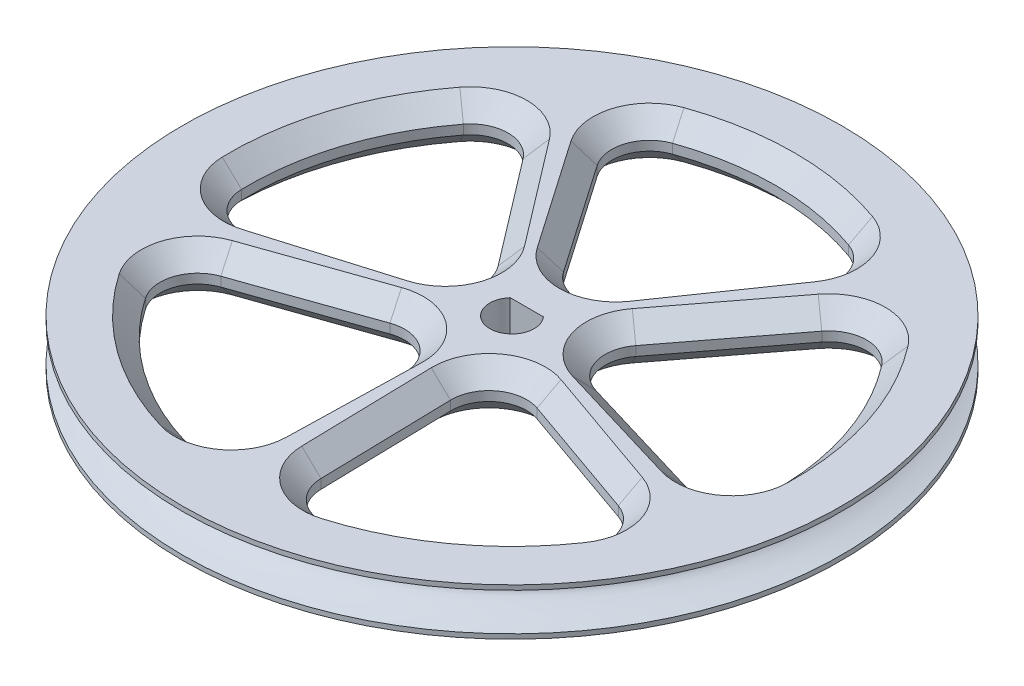
SolidWorks part; units mm, degrees
ref_plane "Front Plane" through (0, 0, 0) normal (0, 0, 1) x (1, 0, 0)
ref_plane "Top Plane" through (0, 0, 0) normal (0, 1, 0) x (1, 0, 0)
ref_plane "Right Plane" through (0, 0, 0) normal (1, 0, 0) x (0, 0, -1)
sketch "Sketch1" plane through (0, 0, 0) normal (0, 1, 0) x (1, 0, 0)
  circle A0 centre (0, 0) radius 22.225
  dimension "D1" = 44.45
extrude "Boss-Extrude1" add sketch "Sketch1" along normal blind 3.175
sketch "Sketch2" plane through (0, 3.175, 0) normal (0, 1, 0) x (1, 0, 0)
  line L0 (-1.118, 1) -> (1.118, 1)
  line L1 (0, 1) -> (0, -1.5) construction
  arc A0 (-1.118, 1) -> (1.118, 1) centre (0, 0) ccw
  dimension "D1" = 3
  dimension "D2" = 2.5
sketch "Sketch3" plane through (0, 3.175, 0) normal (0, 1, 0) x (1, 0, 0)
  line L0 (0, 0) -> (11.1125, 19.2474) construction
  line L1 (0, 0) -> (-11.1125, 19.2474) construction
  line L2 (-7.1774, 12.921) -> (-2.0893, 5.5618)
  line L3 (2.0893, 5.5618) -> (7.1774, 12.921)
  line L4 (0, 2.54) -> (0, 0) construction
  line L5 (0, 0) -> (0, 22.225) construction
  line L6 (10.0706, 10.819) -> (4.6439, 3.7057)
  line L7 (5.9352, -0.2683) -> (14.5066, -2.8333)
  line L8 (13.4014, -6.2345) -> (4.9594, -3.2715)
  line L9 (1.5789, -5.7276) -> (1.7881, -14.6721)
  line L10 (-1.7881, -14.6721) -> (-1.5789, -5.7276)
  line L11 (-4.9594, -3.2715) -> (-13.4014, -6.2345)
  line L12 (-14.5066, -2.8333) -> (-5.9352, -0.2683)
  line L13 (-4.6439, 3.7057) -> (-10.0706, 10.819)
  circle A0 centre (0, 0) radius 22.225 construction
  arc A1 (-5.9362, 16.7598) -> (5.9362, 16.7598) centre (0, 0) cw
  arc A2 (-2.0893, 5.5618) -> (2.0893, 5.5618) centre (0, 7.0063) ccw
  arc A3 (5.9362, 16.7598) -> (7.1774, 12.921) centre (5.0882, 14.3655) cw
  arc A4 (-5.9362, 16.7598) -> (-7.1774, 12.921) centre (-5.0882, 14.3655) ccw
  arc A5 (14.1051, 10.8247) -> (10.0706, 10.819) centre (12.0901, 9.2783) ccw
  arc A6 (14.1051, 10.8247) -> (17.7739, -0.4666) centre (0, 0) cw
  arc A7 (17.7739, -0.4666) -> (14.5066, -2.8333) centre (15.2348, -0.4) cw
  arc A8 (4.6439, 3.7057) -> (5.9352, -0.2683) centre (6.6634, 2.1651) ccw
  arc A9 (14.6536, -10.0697) -> (13.4014, -6.2345) centre (12.5603, -8.6312) ccw
  arc A10 (14.6536, -10.0697) -> (5.0486, -17.0482) centre (0, 0) cw
  arc A11 (5.0486, -17.0482) -> (1.7881, -14.6721) centre (4.3274, -14.6127) cw
  arc A12 (4.9594, -3.2715) -> (1.5789, -5.7276) centre (4.1182, -5.6682) ccw
  arc A13 (-5.0486, -17.0482) -> (-1.7881, -14.6721) centre (-4.3274, -14.6127) ccw
  arc A14 (-5.0486, -17.0482) -> (-14.6536, -10.0697) centre (0, 0) cw
  arc A15 (-14.6536, -10.0697) -> (-13.4014, -6.2345) centre (-12.5603, -8.6312) cw
  arc A16 (-1.5789, -5.7276) -> (-4.9594, -3.2715) centre (-4.1182, -5.6682) ccw
  arc A17 (-17.7739, -0.4666) -> (-14.5066, -2.8333) centre (-15.2348, -0.4) ccw
  arc A18 (-17.7739, -0.4666) -> (-14.1051, 10.8247) centre (0, 0) cw
  arc A19 (-14.1051, 10.8247) -> (-10.0706, 10.819) centre (-12.0901, 9.2783) cw
  arc A20 (-5.9352, -0.2683) -> (-4.6439, 3.7057) centre (-6.6634, 2.1651) ccw
  point P16 (8.89, 15.3979)
  point P19 (-8.89, 15.3979)
  point P59 (0, 0)
  point P60 (0, 0)
  dimension "D2" = 17.78
  dimension "D5" = 2.54
  dimension "D1" = 60
  dimension "D3" = 2.54
  dimension "D4" = 30
  dimension "D6" = 5
extrude "Cut-Extrude2" cut sketch "Sketch3" against normal through all
chamfer "Chamfer2" distance 1.27 angle 45 60 edges at (0, 3.175, -4.4663) (4.6333, 3.175, -9.2414) (7.505, 3.175, -15.147) (-4.6333, 3.175, -9.2414) (-7.505, 3.175, -15.147) (0, 3.175, -17.78) (-4.6333, 0, -9.2414) (-7.505, 0, -15.147) (0, 0, -17.78) (7.505, 0, -15.147) (4.6333, 0, -9.2414) (0, 0, -4.4663) (7.3573, 0, -7.2623) (12.0864, 0, -11.8183) (16.9098, 0, -5.4943) (16.7248, 0, 2.457) (10.2209, 0, 1.5508) (4.2477, 0, -1.3802) (7.3573, 3.175, -7.2623) (12.0864, 3.175, -11.8183) (16.9098, 3.175, -5.4943) (16.7248, 3.175, 2.457) (10.2209, 3.175, 1.5508) (4.2477, 3.175, -1.3802) (9.1804, 0, 4.753) (14.9748, 0, 7.8428) (10.4508, 0, 14.3843) (2.8315, 0, 16.6655) (1.6835, 0, 10.1998) (2.6252, 0, 3.6133) (9.1804, 3.175, 4.753) (14.9748, 3.175, 7.8428) (10.4508, 3.175, 14.3843) (2.8315, 3.175, 16.6655) (1.6835, 3.175, 10.1998) (2.6252, 3.175, 3.6133) (-1.6835, 0, 10.1998) (-2.8315, 0, 16.6655) (-10.4508, 0, 14.3843) (-14.9748, 0, 7.8428) (-9.1804, 0, 4.753) (-2.6252, 0, 3.6133) (-1.6835, 3.175, 10.1998) (-2.8315, 3.175, 16.6655) (-10.4508, 3.175, 14.3843) (-14.9748, 3.175, 7.8428) (-9.1804, 3.175, 4.753) (-2.6252, 3.175, 3.6133) (-10.2209, 0, 1.5508) (-16.7248, 0, 2.457) (-16.9098, 0, -5.4943) (-12.0864, 0, -11.8183) (-7.3573, 0, -7.2623) (-4.2477, 0, -1.3802) (-10.2209, 3.175, 1.5508) (-16.7248, 3.175, 2.457) (-16.9098, 3.175, -5.4943) (-12.0864, 3.175, -11.8183) (-7.3573, 3.175, -7.2623) (-4.2477, 3.175, -1.3802)
sketch "Sketch6" plane through (0, 0, 0) normal (1, 0, 0) x (0, 0, -1)
  line L0 (0, 5.8767) -> (0, -2.5924) construction
  line L1 (-22.225, 3.175) -> (-22.225, 0) construction
  line L2 (-22.225, 2.8575) -> (-22.225, 0.3175)
  line L4 (22.225, 3.175) -> (-22.225, 3.175) construction
  spline S0 degree 2 poles (-22.225, 2.8575) (-18.161, 1.5875) (-22.225, 0.3175) knots 0 0 0 1 1 1
  dimension "D2" = 1.5875
  dimension "D1" = 2.032
  dimension "D3" = 1.27
  dimension "D4" = 1.27
revolve "Cut-Revolve3" cut sketch "Sketch6" angle 360 about L0
extrude "Cut-Extrude4" cut sketch "Sketch2" against normal blind 3.175
